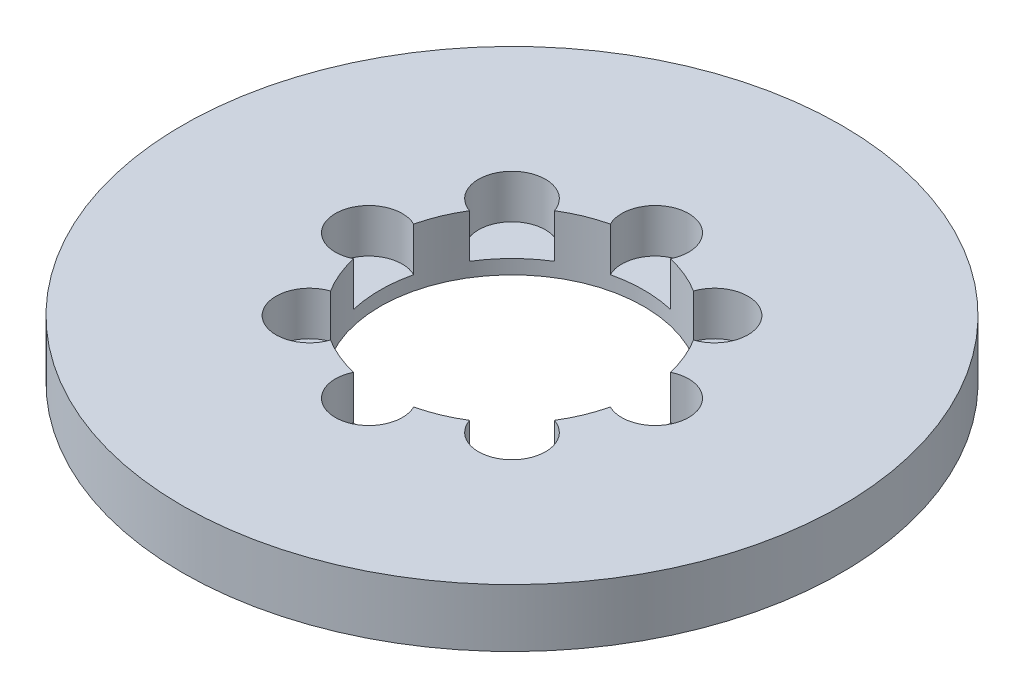
SolidWorks part; units mm, degrees
ref_plane "Front Plane" through (0, 0, 0) normal (0, 0, 1) x (1, 0, 0)
ref_plane "Top Plane" through (0, 0, 0) normal (0, 1, 0) x (1, 0, 0)
ref_plane "Right Plane" through (0, 0, 0) normal (1, 0, 0) x (0, 0, -1)
sketch "Sketch1" plane through (0, 0, 0) normal (0, 1, 0) x (1, 0, 0)
  circle A0 centre (0, 0) radius 62.5
  dimension "FLANGE_OD" = 125
extrude "Boss-Extrude1" add sketch "Sketch1" along normal blind 11
sketch "Sketch2" plane through (0, 0, 0) normal (0, 1, 0) x (1, 0, 0)
  circle A0 centre (0, 0) radius 25
  dimension "BORE_D" = 50
extrude "Cut-Extrude1" cut sketch "Sketch2" along normal through all
sketch "Sketch3" plane through (0, 11, 0) normal (0, 1, 0) x (1, 0, 0)
  circle A0 centre (0, 0) radius 27.1564 construction
  circle A1 centre (-27.1564, 0) radius 6.3517
  dimension "BOLT_D" = 12.7033
  dimension "BOLT_PCD" = 54.3128
extrude "Cut-Extrude2" cut sketch "Sketch3" against normal blind 8.3043
pattern_circular "CirPattern1" count 8 over 360 about axis through (0, 0, 0) along (0, 1, 0) of "Cut-Extrude2"
